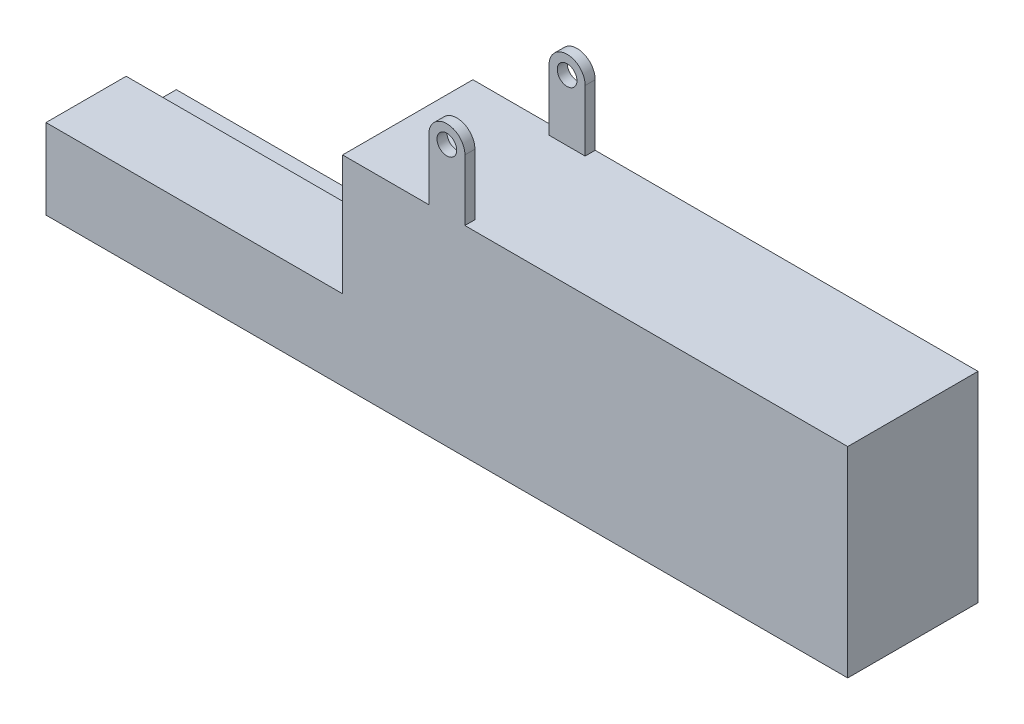
SolidWorks part; units mm, degrees
ref_plane "Front" through (0, 0, 0) normal (0, 0, 1) x (1, 0, 0)
ref_plane "Top" through (0, 0, 0) normal (0, 1, 0) x (1, 0, 0)
ref_plane "Right" through (0, 0, 0) normal (1, 0, 0) x (0, 0, -1)
sketch "Sketch1" plane through (0, 0, 0) normal (0, 1, 0) x (1, 0, 0)
  line L1 (-101.6, 16.51) -> (101.6, 16.51)
  line L2 (-101.6, 16.51) -> (-101.6, -16.51)
  line L3 (-101.6, -16.51) -> (101.6, -16.51)
  line L4 (101.6, 16.51) -> (101.6, -16.51)
  line L5 (-101.6, 16.51) -> (101.6, -16.51) construction
  line L6 (-101.6, -16.51) -> (101.6, 16.51) construction
  point P0 (0, 0)
  dimension "D1" = 33.02
  dimension "D2" = 203.2
extrude "Boss-Extrude1" add sketch "Sketch1" along normal blind 50.8
sketch "Sketch3" plane through (0, 0, 16.51) normal (0, 0, 1) x (1, 0, 0)
  line L2 (0, -18.161) -> (0, 18.161) construction
  line L3 (-4.572, 50.8) -> (-4.572, 66.294)
  line L4 (4.572, 66.294) -> (4.572, 50.8)
  line L5 (-101.6, 0) -> (101.6, 0)
  line L6 (101.6, 0) -> (101.6, 50.8)
  line L7 (101.6, 50.8) -> (-101.6, 50.8)
  line L8 (-101.6, 50.8) -> (-101.6, 0)
  line L9 (-101.6, 0) -> (101.6, 0)
  line L10 (101.6, 0) -> (101.6, 50.8)
  line L11 (101.6, 50.8) -> (-101.6, 50.8)
  line L12 (-101.6, 50.8) -> (-101.6, 0)
  circle A1 centre (0, 66.294) radius 2.5
  arc A2 (-4.572, 66.294) -> (4.572, 66.294) centre (0, 66.294) cw
  point P11 (0, 0)
  dimension "D1" = 0
  dimension "D2" = 15.494
  dimension "D3" = 4.572
sketch "Sketch4" plane through (0, 0, 16.51) normal (0, 0, 1) x (1, 0, 0)
  line L5 (-101.6, 50.8) -> (-26.4257, 50.8)
  line L6 (-101.6, 50.8) -> (-101.6, 11.0309)
  line L7 (-101.6, 11.0309) -> (-26.4257, 11.0309)
  line L8 (-26.4257, 50.8) -> (-26.4257, 11.0309)
  dimension "D1" = 39.7691
extrude "Cut-Extrude2" cut sketch "Sketch4" against normal through all
sketch "Sketch5" plane through (0, 0, 16.51) normal (0, 0, 1) x (1, 0, 0)
  line L6 (-26.4257, 11.0309) -> (-26.4257, 50.8) construction
  line L7 (-101.6, 11.0309) -> (-26.4257, 11.0309)
  line L8 (-101.6, 11.0309) -> (-101.6, 20.32)
  line L9 (-101.6, 20.32) -> (-26.4257, 20.32)
  line L10 (-26.4257, 11.0309) -> (-26.4257, 20.32)
  line L11 (-26.4257, 50.8) -> (101.6, 50.8) construction
  dimension "D1" = 30.48
extrude "Boss-Extrude3" add sketch "Sketch5" against normal blind 20.32 contours L9 L10 L7 L8
sketch "Sketch6" plane through (0, 0, 0) normal (0, 0, 1) x (1, 0, 0)
  line L0 (-4.572, 50.8) -> (-26.4257, 50.8)
  line L1 (-4.572, 50.8) -> (-4.572, 66.294)
  line L2 (4.572, 66.294) -> (4.572, 50.8)
  line L3 (4.572, 50.8) -> (-4.572, 50.8)
  line L9 (-26.4257, 50.8) -> (-26.4257, 20.32)
  line L10 (-26.4257, 20.32) -> (-101.6, 20.32)
  line L11 (-101.6, 20.32) -> (-101.6, 0)
  line L12 (-101.6, 0) -> (101.6, 0)
  line L13 (101.6, 0) -> (101.6, 50.8)
  line L14 (101.6, 50.8) -> (-26.4257, 50.8)
  line L16 (-101.6, 20.32) -> (-101.6, 0)
  line L18 (-26.4257, 50.8) -> (-26.4257, 20.32)
  line L19 (-26.4257, 20.32) -> (-101.6, 20.32)
  line L21 (-101.6, 0) -> (101.6, 0)
  line L22 (101.6, 0) -> (101.6, 50.8)
  line L23 (101.6, 50.8) -> (-26.4257, 50.8)
  circle A0 centre (0, 66.294) radius 2.5
  arc A1 (-4.572, 66.294) -> (4.572, 66.294) centre (0, 66.294) cw
  circle A3 centre (0, 66.294) radius 2.5
  dimension "D1" = 0
extrude "Boss-Extrude4" add sketch "Sketch6" along normal mid plane 2.54 from offset 15.24 contours L0 A0 region at (0, 59.6186, 0)
extrude "Boss-Extrude5" add sketch "Sketch6<3>" along normal mid plane 2.54 from offset 15.24 contours L1 A1 L2 L3 | A0 offset against normal yes
sketch "Sketch6<3>" plane through (0, 0, 0) normal (0, 0, 1) x (1, 0, 0) same geometry as "Sketch6"
